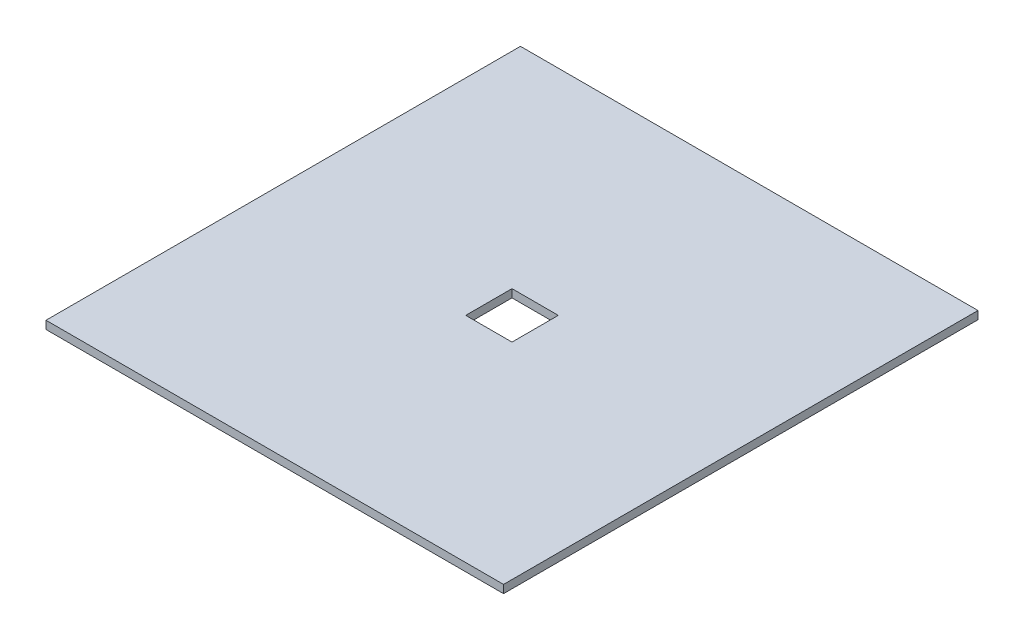
SolidWorks part; units mm, degrees
material "PVC Rigid"
ref_plane "Front" through (0, 0, 0) normal (0, 0, 1) x (1, 0, 0)
ref_plane "Top" through (0, 0, 0) normal (0, 1, 0) x (1, 0, 0)
ref_plane "Right" through (0, 0, 0) normal (1, 0, 0) x (0, 0, -1)
sketch "Sketch1" plane through (0, 0, 0) normal (0, 1, 0) x (1, 0, 0)
  line L1 (-90.3859, -93.726) -> (90.3859, -93.726)
  line L2 (-90.3859, -93.726) -> (-90.3859, 93.726)
  line L3 (-90.3859, 93.726) -> (90.3859, 93.726)
  line L4 (90.3859, -93.726) -> (90.3859, 93.726)
  line L5 (-90.3859, -93.726) -> (90.3859, 93.726) construction
  line L6 (-90.3859, 93.726) -> (90.3859, -93.726) construction
  point P0 (0, 0)
  dimension "D1" = 180.7718
  dimension "D2" = 187.452
extrude "Boss-Extrude1" add sketch "Sketch1" along normal blind 3.175
sketch "Sketch2" plane through (0, 3.175, 0) normal (0, 1, 0) x (1, 0, 0)
  line L0 (-90.3859, 93.726) -> (90.3859, -93.726) construction
  line L2 (-9.144, -9.144) -> (9.144, -9.144)
  line L3 (-9.144, -9.144) -> (-9.144, 9.144)
  line L4 (-9.144, 9.144) -> (9.144, 9.144)
  line L5 (9.144, -9.144) -> (9.144, 9.144)
  line L6 (-9.144, -9.144) -> (9.144, 9.144) construction
  line L7 (-9.144, 9.144) -> (9.144, -9.144) construction
  point P4 (0, 0)
  point P10 (0, 0)
  dimension "D1" = 18.288
  dimension "D2" = 18.288
extrude "Cut-Extrude1" cut sketch "Sketch2" against normal blind 3.175
sketch "Sketch3" plane through (0, 3.175, 0) normal (0, 1, 0) x (1, 0, 0)
  line L0 (9.144, -9.144) -> (8.0215, -9.144) construction
  line L6 (-9.144, -9.144) -> (9.144, -9.144) construction
  line L7 (9.144, -9.144) -> (9.144, -8.0215) construction
  line L8 (9.144, -9.144) -> (9.144, 9.144) construction
  line L9 (9.144, 0) -> (-9.144, 0) construction
  line L10 (-9.144, 9.144) -> (-9.144, -9.144) construction
  line L11 (0, -9.144) -> (0, 9.144) construction
  line L12 (9.144, 9.144) -> (-9.144, 9.144) construction
  circle A4 centre (8.5827, -8.5827) radius 0.7937
  circle A5 centre (-8.5827, -8.5827) radius 0.7937
  circle A6 centre (-8.5827, 8.5827) radius 0.7937
  circle A7 centre (8.5827, 8.5827) radius 0.7937
  dimension "D1" = 1.5875
extrude "Cut-Extrude2" [suppressed] cut sketch "Sketch3" against normal through all
sketch "Sketch8" plane through (0, 3.175, 0) normal (0, 1, 0) x (1, 0, 0)
  line L0 (90.3859, -93.726) -> (-90.3859, 93.726) construction
  line L2 (49.2125, 49.2125) -> (-49.2125, 49.2125) construction
  line L3 (49.2125, 49.2125) -> (49.2125, -49.2125) construction
  line L4 (49.2125, -49.2125) -> (-49.2125, -49.2125) construction
  line L5 (-49.2125, 49.2125) -> (-49.2125, -49.2125) construction
  line L6 (49.2125, 49.2125) -> (-49.2125, -49.2125) construction
  line L7 (49.2125, -49.2125) -> (-49.2125, 49.2125) construction
  point P4 (0, 0)
  point P11 (-49.2125, -49.2125)
  point P12 (-49.2125, 49.2125)
  point P13 (49.2125, 49.2125)
  point P14 (49.2125, -49.2125)
  dimension "D1" = 98.425
pattern_sketch "Sketch-Pattern1" [suppressed] of bodies 181 driven by "Sketch8"
sketch "Sketch4" plane through (0, 3.175, 0) normal (0, 1, 0) x (1, 0, 0)
  line L0 (-87.8459, -91.186) -> (90.3859, -91.186) construction
  line L1 (-90.3859, -93.726) -> (-87.8459, -93.726) construction
  line L2 (-90.3859, -93.726) -> (-90.3859, -91.186) construction
  line L3 (-90.3859, -91.186) -> (-87.8459, -91.186) construction
  line L4 (-87.8459, -93.726) -> (-87.8459, -91.186) construction
  line L5 (90.3859, -93.726) -> (90.3859, 93.726) construction
  text T0 "TR" font "Consolas" height 3.175
  dimension "D1" = 2.54
extrude "Cut-Extrude3" [suppressed] cut sketch "Sketch4" against normal blind 1.5875
sketch "Sketch9" plane through (0, 3.175, 0) normal (0, 1, 0) x (1, 0, 0)
  line L0 (-90.3859, 93.726) -> (-90.3859, -93.726) construction
  line L1 (-90.3859, -93.726) -> (90.3859, -93.726) construction
  circle A0 centre (-87.8459, -91.186) radius 0.7937
  dimension "D1" = 1.5875
  dimension "D2" = 2.54
  dimension "D3" = 2.54
extrude "Cut-Extrude4" [suppressed] cut sketch "Sketch9" against normal blind 1.27
pattern_linear "LPattern1" [suppressed] count 4 spacing 2.54 of bodies 184
